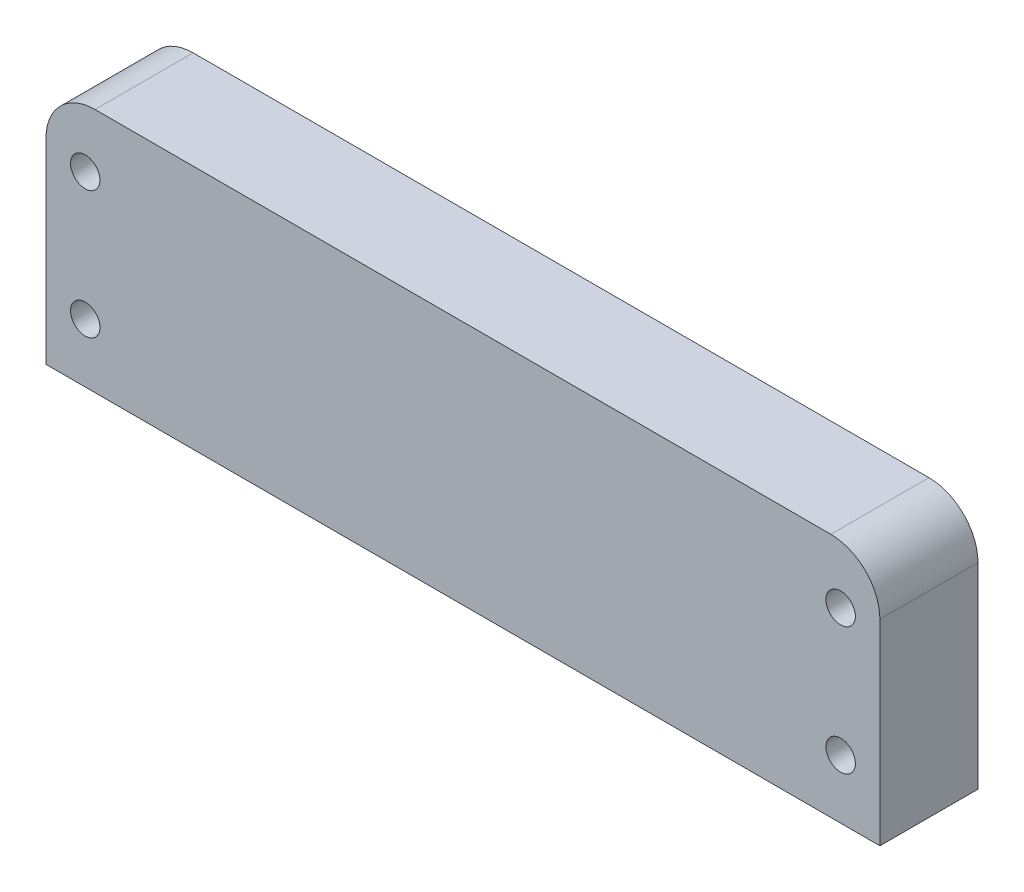
SolidWorks part; units mm, degrees
ref_plane "Спереди" through (0, 0, 0) normal (0, 0, 1) x (1, 0, 0)
ref_plane "Сверху" through (0, 0, 0) normal (0, 1, 0) x (1, 0, 0)
ref_plane "Справа" through (0, 0, 0) normal (1, 0, 0) x (0, 0, -1)
sketch "Эскиз1" plane through (0, 0, 0) normal (0, 0, 1) x (1, 0, 0)
  line L1 (-42.5, -12.5) -> (42.5, -12.5)
  line L2 (-42.5, -12.5) -> (-42.5, 12.5)
  line L3 (-42.5, 12.5) -> (42.5, 12.5)
  line L4 (42.5, -12.5) -> (42.5, 12.5)
  line L5 (-42.5, -12.5) -> (42.5, 12.5) construction
  line L6 (-42.5, 12.5) -> (42.5, -12.5) construction
  point P0 (0, 0)
  dimension "D1" = 85
  dimension "D2" = 25
extrude "основание для камеры" add sketch "Эскиз1" along normal blind 5 and the other way blind 5
sketch "Эскиз4" plane through (0, 0, 5) normal (0, 0, 1) x (1, 0, 0)
  line L1 (-38.5, -6.5) -> (38.5, -6.5) construction
  line L2 (-38.5, -6.5) -> (-38.5, 6.5) construction
  line L3 (-38.5, 6.5) -> (38.5, 6.5) construction
  line L4 (38.5, -6.5) -> (38.5, 6.5) construction
  line L5 (-38.5, -6.5) -> (38.5, 6.5) construction
  line L6 (-38.5, 6.5) -> (38.5, -6.5) construction
  circle A0 centre (-38.5, 6.5) radius 1.5
  circle A1 centre (38.5, 6.5) radius 1.5
  circle A2 centre (38.5, -6.5) radius 1.5
  circle A3 centre (-38.5, -6.5) radius 1.5
  point P0 (0, 0)
  dimension "D3" = 3
  dimension "D1" = 77
  dimension "D2" = 13
extrude "крепление камеры" cut sketch "Эскиз4" against normal through all
sketch "Эскиз6" plane through (0, -12.5, 0) normal (0, -1, 0) x (1, 0, 0)
  line L0 (-20, 0) -> (20, 0) construction
  circle A0 centre (-20, 0) radius 1.25
  circle A1 centre (20, 0) radius 1.25
  point P4 (0, 0)
  dimension "D2" = 40
  dimension "D1" = 2.5
extrude "крепление к корпусу" cut sketch "Эскиз6" against normal blind 10
fillet "Скругление2" radius 5 2 edges at (-42.5, 12.5, 0) (42.5, 12.5, 0)
